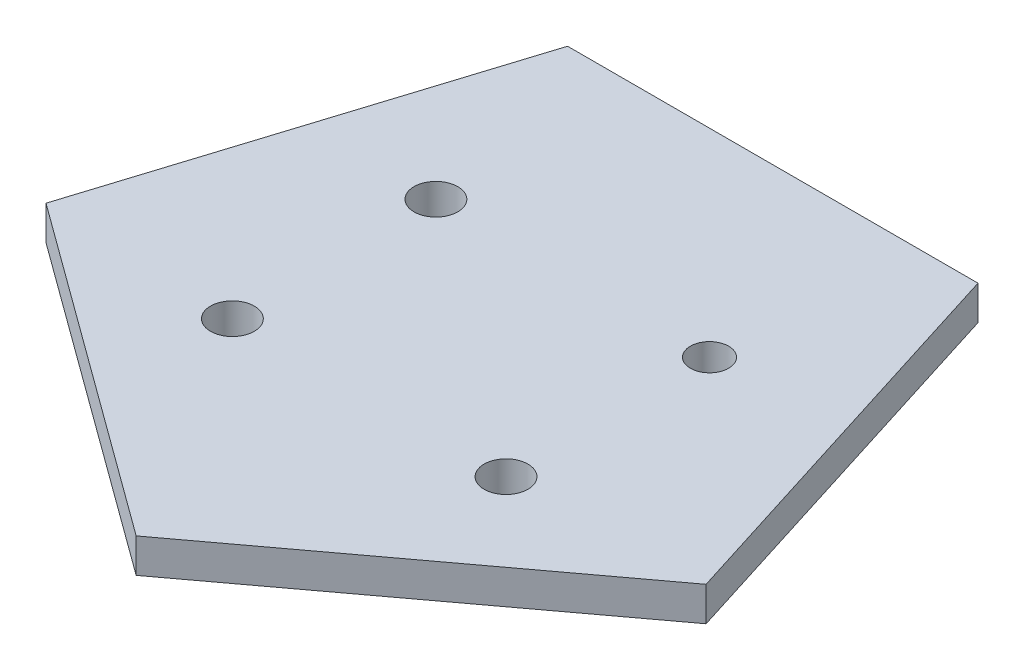
SolidWorks part; units mm, degrees
ref_plane "Front Plane" through (0, 0, 0) normal (0, 0, 1) x (1, 0, 0)
ref_plane "Top Plane" through (0, 0, 0) normal (0, 1, 0) x (1, 0, 0)
ref_plane "Right Plane" through (0, 0, 0) normal (1, 0, 0) x (0, 0, -1)
sketch "Sketch1" plane through (0, 0, 0) normal (0, 1, 0) x (1, 0, 0)
  line L0 (0, 0) -> (-11.5887, -36.83)
  line L5 (-11.5887, -36.83) -> (19.3437, -59.3912)
  line L13 (-11.5888, -36.83) -> (9.525, -48.5193) construction
  line L14 (19.3437, -59.3912) -> (49.6887, -36.83)
  line L15 (-69.987, -36.83) -> (-11.5888, -36.83) construction
  line L17 (49.6887, -36.83) -> (38.1, 0)
  line L18 (38.1, 0) -> (0, 0)
  line L19 (9.525, -59.3912) -> (29.1625, -59.3912) construction
  dimension "D1" = 38.1
extrude "Boss-Extrude1" add sketch "Sketch1" along normal mid plane 3.175
sketch "Sketch2" plane through (0, 1.5875, 0) normal (0, 1, 0) x (1, 0, 0)
  circle A0 centre (31.5913, -18.415) radius 1.778
  circle A1 centre (6.1913, -18.415) radius 2.032
  circle A2 centre (6.35, -37.465) radius 2.032
  circle A3 centre (31.75, -37.465) radius 2.032
  dimension "D1" = 3.556
  dimension "D3" = 4.064
extrude "Cut-Extrude1" cut sketch "Sketch2" against normal through all
